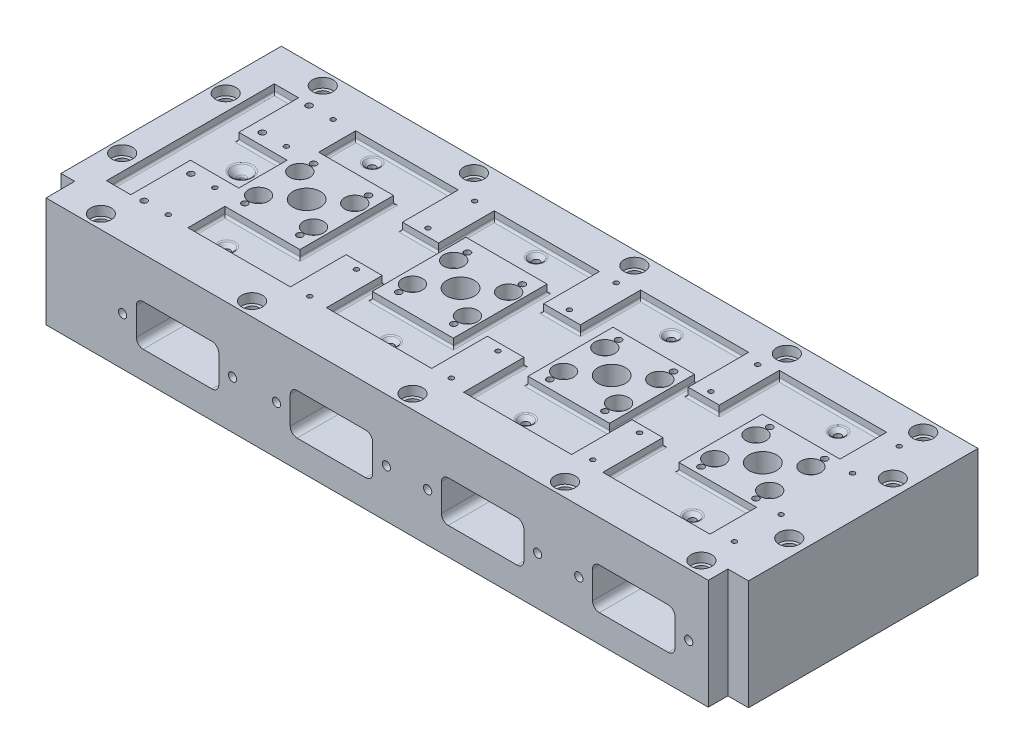
SolidWorks part; units mm, degrees
ref_plane "Alzado" through (0, 0, 0) normal (0, 0, 1) x (1, 0, 0)
ref_plane "Planta" through (0, 0, 0) normal (0, 1, 0) x (1, 0, 0)
ref_plane "Vista lateral" through (0, 0, 0) normal (1, 0, 0) x (0, 0, -1)
sketch "Croquis1" plane through (0, 0, 0) normal (0, 1, 0) x (1, 0, 0)
  line L0 (0, 160.36) -> (0, 0)
  line L1 (0, 0) -> (10, 0)
  line L2 (10, 0) -> (10, -20.92)
  line L3 (10, -20.92) -> (492, -20.92)
  line L4 (492, -20.92) -> (492, -6.67)
  line L5 (492, -6.67) -> (507, -6.67)
  line L6 (507, -6.67) -> (507, 160.36)
  line L7 (507, 160.36) -> (0, 160.36)
  dimension "D1" = 10
  dimension "D2" = 15
  dimension "D3" = 160.36
  dimension "D4" = 507
  dimension "D5" = 14.25
  dimension "D6" = 20.92
extrude "Saliente-Extruir1" add sketch "Croquis1" along normal blind 80
sketch "Croquis2" plane through (0, 80, 0) normal (0, 1, 0) x (1, 0, 0)
  line L0 (507, 160.36) -> (0, 160.36) construction
  line L1 (0, 160.36) -> (0, 0) construction
  line L2 (507, -6.67) -> (507, 160.36) construction
  circle A0 centre (105.75, 75.12) radius 42.9
  circle A1 centre (217.75, 75.12) radius 42.9
  circle A2 centre (327.75, 75.12) radius 42.9
  circle A3 centre (437.75, 75.12) radius 42.9
  point P13 (0, 80.18)
  dimension "D1" = 85.8
  dimension "D2" = 85.24
  dimension "D3" = 105.75
  dimension "D4" = 112
  dimension "D5" = 110
  dimension "D6" = 69.25
sketch "Croquis3" plane through (0, 0, 0) normal (0, -1, 0) x (1, 0, 0)
  circle A0 centre (437.75, -75.12) radius 42.9 construction
  circle A1 centre (327.75, -75.12) radius 42.9 construction
  circle A2 centre (217.75, -75.12) radius 42.9 construction
  circle A3 centre (105.75, -75.12) radius 42.9 construction
  circle A4 centre (437.75, -75.12) radius 42.9
  circle A5 centre (327.75, -75.12) radius 42.9
  circle A6 centre (217.75, -75.12) radius 42.9
  circle A7 centre (105.75, -75.12) radius 42.9
extrude "Cortar-Extruir2" cut sketch "Croquis3" against normal blind 1.5
sketch "Croquis4" plane through (0, 80, 0) normal (0, 1, 0) x (1, 0, 0)
  circle A0 centre (105.75, 75.12) radius 42.9 construction
  circle A1 centre (217.75, 75.12) radius 42.9 construction
  circle A2 centre (327.75, 75.12) radius 42.9 construction
  circle A3 centre (437.75, 75.12) radius 42.9 construction
  circle A4 centre (105.75, 75.12) radius 42.9
  circle A5 centre (217.75, 75.12) radius 42.9
  circle A6 centre (327.75, 75.12) radius 42.9
  circle A7 centre (437.75, 75.12) radius 42.9
sketch "Croquis5" plane through (0, 80, 0) normal (0, 1, 0) x (1, 0, 0)
  line L0 (85.75, 58.02) -> (125.75, 58.02) construction
  line L1 (197.75, 58.02) -> (237.75, 58.02) construction
  line L2 (307.75, 58.02) -> (347.75, 58.02) construction
  line L3 (417.75, 58.02) -> (457.75, 58.02) construction
  circle A0 centre (437.75, 75.12) radius 42.9 construction
  circle A1 centre (327.75, 75.12) radius 42.9 construction
  circle A2 centre (217.75, 75.12) radius 42.9 construction
  circle A3 centre (105.75, 75.12) radius 42.9 construction
  circle A4 centre (437.75, 75.12) radius 42.9 construction
  circle A5 centre (327.75, 75.12) radius 42.9 construction
  circle A6 centre (217.75, 75.12) radius 42.9 construction
  circle A7 centre (105.75, 75.12) radius 42.9 construction
  circle A8 centre (85.75, 88.02) radius 3
  circle A9 centre (125.75, 88.02) radius 3
  circle A10 centre (85.75, 58.02) radius 3
  circle A11 centre (125.75, 58.02) radius 3
  circle A12 centre (237.75, 88.02) radius 3
  circle A13 centre (197.75, 58.02) radius 3
  circle A14 centre (237.75, 58.02) radius 3
  circle A15 centre (197.75, 88.02) radius 3
  circle A16 centre (347.75, 88.02) radius 3
  circle A17 centre (307.75, 58.02) radius 3
  circle A18 centre (347.75, 58.02) radius 3
  circle A19 centre (307.75, 88.02) radius 3
  circle A20 centre (457.75, 88.02) radius 3
  circle A21 centre (417.75, 58.02) radius 3
  circle A22 centre (457.75, 58.02) radius 3
  circle A23 centre (417.75, 88.02) radius 3
  point P20 (105.75, 58.02)
  point P21 (105.75, 118.02)
  point P22 (217.75, 118.02)
  point P23 (327.75, 118.02)
  point P24 (437.75, 118.02)
  point P33 (437.75, 58.02)
  point P42 (327.75, 58.02)
  point P53 (217.75, 58.02)
  point P54 (437.75, 75.12)
  point P55 (217.75, 58.02)
  point P56 (437.75, 58.02)
  point P57 (327.75, 58.02)
  dimension "D3" = 6
  dimension "D8" = 6
  dimension "D10" = 30
  dimension "D12" = 6
  dimension "D14" = 6
  dimension "D15" = 30
  dimension "D1" = 30
  dimension "D2" = 40
  dimension "D4" = 30
  dimension "D5" = 30
  dimension "D6" = 40
  dimension "D7" = 30
  dimension "D9" = 40
  dimension "D11" = 30
  dimension "D13" = 40
  dimension "D16" = 30
extrude "Cortar-Extruir3" cut sketch "Croquis5" against normal blind 77
sketch "Croquis6" plane through (0, 1.5, 0) normal (0, -1, 0) x (1, 0, 0)
  circle A0 centre (85.75, -88.02) radius 14
  circle A1 centre (125.75, -88.02) radius 14
  circle A2 centre (125.75, -58.02) radius 14
  circle A4 centre (85.75, -58.02) radius 14
  circle A5 centre (197.75, -58.02) radius 14
  circle A6 centre (197.75, -88.02) radius 14
  circle A7 centre (237.75, -88.02) radius 14
  circle A8 centre (237.75, -58.02) radius 14
  circle A9 centre (307.75, -58.02) radius 14
  circle A10 centre (307.75, -88.02) radius 14
  circle A11 centre (347.75, -88.02) radius 14
  circle A12 centre (347.75, -58.02) radius 14
  circle A13 centre (457.75, -88.02) radius 14
  circle A14 centre (417.75, -88.02) radius 14
  circle A15 centre (417.75, -58.02) radius 14
  circle A17 centre (457.75, -58.02) radius 14
  dimension "D1" = 28
extrude "Cortar-Extruir4" cut sketch "Croquis6" against normal up to surface (1.5 mm away) up to face at (85.75, 3, -55.02)
chamfer "Chaflán1" distance 1.5 distance2 10 16 edges at (417.75, 3, -44.02) (457.75, 3, -44.02) (457.75, 3, -74.02) (417.75, 3, -74.02) (307.75, 3, -74.02) (307.75, 3, -44.02) (347.75, 3, -74.02) (347.75, 3, -44.02) (237.75, 3, -74.02) (237.75, 3, -44.02) (197.75, 3, -74.02) (197.75, 3, -44.02) (125.75, 3, -44.02) (85.75, 3, -44.02) (125.75, 3, -74.02) (85.75, 3, -74.02)
sketch "Croquis7" plane through (0, 0, 20.92) normal (0, 0, 1) x (1, 0, 0)
  line L0 (10, 0) -> (492, 0) construction
  line L1 (80.75, 50) -> (130.75, 50)
  line L2 (75.75, 45) -> (75.75, 25)
  line L3 (80.75, 20) -> (130.75, 20)
  line L4 (135.75, 45) -> (135.75, 25)
  line L5 (75.75, 50) -> (135.75, 20) construction
  line L6 (75.75, 20) -> (135.75, 50) construction
  line L7 (192.75, 50) -> (242.75, 50)
  line L8 (187.75, 45) -> (187.75, 25)
  line L9 (192.75, 20) -> (242.75, 20)
  line L10 (247.75, 45) -> (247.75, 25)
  line L11 (187.75, 50) -> (247.75, 20) construction
  line L12 (187.75, 20) -> (247.75, 50) construction
  line L13 (302.75, 50) -> (352.75, 50)
  line L14 (297.75, 45) -> (297.75, 25)
  line L15 (302.75, 20) -> (352.75, 20)
  line L16 (357.75, 45) -> (357.75, 25)
  line L17 (297.75, 50) -> (357.75, 20) construction
  line L18 (297.75, 20) -> (357.75, 50) construction
  line L19 (412.75, 50) -> (462.75, 50)
  line L20 (407.75, 45) -> (407.75, 25)
  line L21 (412.75, 20) -> (462.75, 20)
  line L22 (467.75, 45) -> (467.75, 25)
  line L23 (407.75, 50) -> (467.75, 20) construction
  line L24 (407.75, 20) -> (467.75, 50) construction
  arc A0 (130.75, 50) -> (135.75, 45) centre (130.75, 45) cw
  arc A1 (130.75, 20) -> (135.75, 25) centre (130.75, 25) ccw
  arc A2 (80.75, 50) -> (75.75, 45) centre (80.75, 45) ccw
  arc A3 (75.75, 25) -> (80.75, 20) centre (80.75, 25) ccw
  arc A4 (192.75, 50) -> (187.75, 45) centre (192.75, 45) ccw
  arc A5 (242.75, 50) -> (247.75, 45) centre (242.75, 45) cw
  arc A6 (242.75, 20) -> (247.75, 25) centre (242.75, 25) ccw
  arc A7 (187.75, 25) -> (192.75, 20) centre (192.75, 25) ccw
  arc A8 (462.75, 50) -> (467.75, 45) centre (462.75, 45) cw
  arc A9 (462.75, 20) -> (467.75, 25) centre (462.75, 25) ccw
  arc A10 (412.75, 50) -> (407.75, 45) centre (412.75, 45) ccw
  arc A11 (407.75, 25) -> (412.75, 20) centre (412.75, 25) ccw
  arc A12 (297.75, 25) -> (302.75, 20) centre (302.75, 25) ccw
  arc A13 (352.75, 50) -> (357.75, 45) centre (352.75, 45) cw
  arc A14 (352.75, 20) -> (357.75, 25) centre (352.75, 25) ccw
  arc A15 (302.75, 50) -> (297.75, 45) centre (302.75, 45) ccw
  point P0 (105.75, 35)
  point P5 (217.75, 35)
  point P10 (327.75, 35)
  point P15 (437.75, 35)
  point P23 (437.75, 80)
  point P24 (327.75, 80)
  point P27 (217.75, 80)
  point P29 (105.75, 80)
  dimension "D4" = 5
  dimension "D1" = 30
  dimension "D2" = 60
  dimension "D3" = 20
extrude "Cortar-Extruir5" cut sketch "Croquis7" against normal blind 100
sketch "Croquis8" plane through (0, 0, -160.36) normal (0, 0, -1) x (-1, 0, 0)
  line L0 (-462.75, 50) -> (-412.75, 50) construction
  line L1 (-407.75, 45) -> (-407.75, 25) construction
  line L2 (-412.75, 20) -> (-462.75, 20) construction
  line L3 (-467.75, 25) -> (-467.75, 45) construction
  line L4 (-302.75, 20) -> (-352.75, 20) construction
  line L5 (-357.75, 25) -> (-357.75, 45) construction
  line L6 (-352.75, 50) -> (-302.75, 50) construction
  line L7 (-297.75, 45) -> (-297.75, 25) construction
  line L8 (-187.75, 45) -> (-187.75, 25) construction
  line L9 (-192.75, 20) -> (-242.75, 20) construction
  line L10 (-247.75, 25) -> (-247.75, 45) construction
  line L11 (-242.75, 50) -> (-192.75, 50) construction
  line L12 (-130.75, 50) -> (-80.75, 50) construction
  line L13 (-75.75, 45) -> (-75.75, 25) construction
  line L14 (-80.75, 20) -> (-130.75, 20) construction
  line L15 (-135.75, 25) -> (-135.75, 45) construction
  line L16 (-462.75, 50) -> (-412.75, 50)
  line L17 (-407.75, 45) -> (-407.75, 25)
  line L18 (-412.75, 20) -> (-462.75, 20)
  line L19 (-467.75, 25) -> (-467.75, 45)
  line L20 (-302.75, 20) -> (-352.75, 20)
  line L21 (-357.75, 25) -> (-357.75, 45)
  line L22 (-352.75, 50) -> (-302.75, 50)
  line L23 (-297.75, 45) -> (-297.75, 25)
  line L24 (-187.75, 45) -> (-187.75, 25)
  line L25 (-192.75, 20) -> (-242.75, 20)
  line L26 (-247.75, 25) -> (-247.75, 45)
  line L27 (-242.75, 50) -> (-192.75, 50)
  line L28 (-130.75, 50) -> (-80.75, 50)
  line L29 (-75.75, 45) -> (-75.75, 25)
  line L30 (-80.75, 20) -> (-130.75, 20)
  line L31 (-135.75, 25) -> (-135.75, 45)
  arc A0 (-462.75, 50) -> (-467.75, 45) centre (-462.75, 45) ccw construction
  arc A1 (-407.75, 45) -> (-412.75, 50) centre (-412.75, 45) ccw construction
  arc A2 (-412.75, 20) -> (-407.75, 25) centre (-412.75, 25) ccw construction
  arc A3 (-467.75, 25) -> (-462.75, 20) centre (-462.75, 25) ccw construction
  arc A4 (-302.75, 20) -> (-297.75, 25) centre (-302.75, 25) ccw construction
  arc A5 (-357.75, 25) -> (-352.75, 20) centre (-352.75, 25) ccw construction
  arc A6 (-352.75, 50) -> (-357.75, 45) centre (-352.75, 45) ccw construction
  arc A7 (-297.75, 45) -> (-302.75, 50) centre (-302.75, 45) ccw construction
  arc A8 (-187.75, 45) -> (-192.75, 50) centre (-192.75, 45) ccw construction
  arc A9 (-192.75, 20) -> (-187.75, 25) centre (-192.75, 25) ccw construction
  arc A10 (-247.75, 25) -> (-242.75, 20) centre (-242.75, 25) ccw construction
  arc A11 (-242.75, 50) -> (-247.75, 45) centre (-242.75, 45) ccw construction
  arc A12 (-130.75, 50) -> (-135.75, 45) centre (-130.75, 45) ccw construction
  arc A13 (-75.75, 45) -> (-80.75, 50) centre (-80.75, 45) ccw construction
  arc A14 (-80.75, 20) -> (-75.75, 25) centre (-80.75, 25) ccw construction
  arc A15 (-135.75, 25) -> (-130.75, 20) centre (-130.75, 25) ccw construction
  arc A16 (-462.75, 50) -> (-467.75, 45) centre (-462.75, 45) ccw
  arc A17 (-407.75, 45) -> (-412.75, 50) centre (-412.75, 45) ccw
  arc A18 (-412.75, 20) -> (-407.75, 25) centre (-412.75, 25) ccw
  arc A19 (-467.75, 25) -> (-462.75, 20) centre (-462.75, 25) ccw
  arc A20 (-302.75, 20) -> (-297.75, 25) centre (-302.75, 25) ccw
  arc A21 (-357.75, 25) -> (-352.75, 20) centre (-352.75, 25) ccw
  arc A22 (-352.75, 50) -> (-357.75, 45) centre (-352.75, 45) ccw
  arc A23 (-297.75, 45) -> (-302.75, 50) centre (-302.75, 45) ccw
  arc A24 (-187.75, 45) -> (-192.75, 50) centre (-192.75, 45) ccw
  arc A25 (-192.75, 20) -> (-187.75, 25) centre (-192.75, 25) ccw
  arc A26 (-247.75, 25) -> (-242.75, 20) centre (-242.75, 25) ccw
  arc A27 (-242.75, 50) -> (-247.75, 45) centre (-242.75, 45) ccw
  arc A28 (-130.75, 50) -> (-135.75, 45) centre (-130.75, 45) ccw
  arc A29 (-75.75, 45) -> (-80.75, 50) centre (-80.75, 45) ccw
  arc A30 (-80.75, 20) -> (-75.75, 25) centre (-80.75, 25) ccw
  arc A31 (-135.75, 25) -> (-130.75, 20) centre (-130.75, 25) ccw
extrude "Cortar-Extruir6" cut sketch "Croquis8" against normal blind 78.59
sketch "Croquis9" plane through (0, 1.5, 0) normal (0, -1, 0) x (1, 0, 0)
  circle A0 centre (85.75, -58.02) radius 7.5
  circle A1 centre (125.75, -58.02) radius 7.5
  circle A2 centre (85.75, -88.02) radius 7.5
  circle A3 centre (125.75, -88.02) radius 7.5
  circle A4 centre (197.75, -88.02) radius 7.5
  circle A5 centre (197.75, -58.02) radius 7.5
  circle A6 centre (237.75, -88.02) radius 7.5
  circle A7 centre (237.75, -58.02) radius 7.5
  circle A8 centre (347.75, -58.02) radius 7.5
  circle A9 centre (307.75, -58.02) radius 7.5
  circle A10 centre (307.75, -88.02) radius 7.5
  circle A11 centre (347.75, -88.02) radius 7.5
  circle A12 centre (417.75, -58.02) radius 7.5
  circle A13 centre (417.75, -88.02) radius 7.5
  circle A14 centre (457.75, -88.02) radius 7.5
  circle A15 centre (457.75, -58.02) radius 7.5
  dimension "D1" = 15
extrude "Cortar-Extruir7" cut sketch "Croquis9" against normal up to surface (48.5 mm away) up to face at (85.75, 50, -55.02)
sketch "Croquis10" plane through (0, 80, 0) normal (0, 1, 0) x (1, 0, 0)
  line L0 (0, 140.61) -> (19, 140.61) construction
  line L1 (0, 160.36) -> (0, 0) construction
  line L2 (19, 140.61) -> (19, 160.36) construction
  line L3 (507, 160.36) -> (0, 160.36) construction
  line L4 (0, 0) -> (10, 0) construction
  line L5 (507, -6.67) -> (507, 160.36) construction
  line L6 (507, 160.36) -> (483, 160.36) construction
  line L7 (10, -20.92) -> (10, -1.01) construction
  point P0 (40, -10.965)
  point P1 (150, -10.965)
  point P2 (266.75, -10.965)
  point P3 (377.75, -10.965)
  point P4 (477, -10.965)
  point P5 (495, 35)
  point P6 (495, 110.36)
  point P7 (477, 150.485)
  point P8 (377.75, 150.485)
  point P9 (266.75, 150.485)
  point P10 (150, 150.485)
  point P11 (40, 150.485)
  point P12 (9.5, 110.36)
  point P13 (9.5, 35)
  point P19 (495, 160.36)
  point P24 (9.5, 140.61)
  point P33 (10, -10.965)
  point P34 (19, 150.485)
  dimension "D1" = 19.75
  dimension "D2" = 19
  dimension "D3" = 35
  dimension "D4" = 50
  dimension "D5" = 40
  dimension "D6" = 110
  dimension "D7" = 116.75
  dimension "D8" = 111
  dimension "D9" = 30
  dimension "D10" = 24
  dimension "D11" = 19.91
hole_wizard "Refrentado para perno con cabeza hexagonal de M101" positions "Croquis3D1" profile "Croquis11" counterbore size "M10" standard "Ansi Metric"
sketch3d "Croquis3D1"
  point P0 (40, 80, -150.485)
  point P3 (9.5, 80, -110.36)
  point P6 (9.5, 80, -35)
  point P9 (40, 80, 10.965)
  point P12 (150, 80, 10.965)
  point P15 (266.75, 80, 10.965)
  point P18 (377.75, 80, 10.965)
  point P21 (477, 80, 10.965)
  point P24 (495, 80, -35)
  point P27 (495, 80, -110.36)
  point P30 (477, 80, -150.485)
  point P33 (377.75, 80, -150.485)
  point P36 (266.75, 80, -150.485)
  point P39 (150, 80, -150.485)
sketch "Croquis11" plane through (40, 80, -150.485) normal (1, 0, 0) x (0, 0, 1)
  line L0 (0, 0) -> (0, 93.1545)
  line L1 (0, 93.1545) -> (5.25, 90)
  line L2 (5.25, 90) -> (5.25, 6.85)
  line L3 (5.25, 6.85) -> (7.5, 6.85)
  line L4 (7.5, 6.85) -> (7.5, 0)
  line L5 (7.5, 0) -> (0, 0)
  line L10 (0, 93.1545) -> (-5.25, 90) construction
  line L11 (0, -6.35) -> (0, 107.95) construction
  dimension "Diámetro de taladro" = 10.5
  dimension "Profundidad de taladro" = 90
  dimension "Diámetro de refrentado" = 15
  dimension "Profundidad de refrentado" = 6.85
  dimension "Ángulo de perforador" = 118
sketch "Croquis12" plane through (0, 80, 0) normal (0, 1, 0) x (1, 0, 0)
  line L0 (477, 99.02) -> (477, 133.02) construction
  line L2 (507, -6.67) -> (507, 160.36) construction
  line L3 (374, 99.02) -> (374, 133.02) construction
  line L4 (271, 99.02) -> (271, 133.02) construction
  line L5 (168, 99.02) -> (168, 133.02) construction
  line L6 (65, 99.02) -> (65, 133.02) construction
  line L7 (417.75, 58.02) -> (417.75, 88.02) construction
  line L8 (417.75, 73.02) -> (362.9429, 73.02) construction
  circle A0 centre (457.75, 88.02) radius 3 construction
  circle A1 centre (417.75, 88.02) radius 3 construction
  point P2 (477, 116.02)
  point P17 (374, 116.02)
  dimension "D1" = 28
  dimension "D2" = 34
  dimension "D3" = 30
  dimension "D5" = 103
  dimension "D6" = 28
  dimension "D4" = 5
hole_wizard "Taladro de margen para M31" positions "Croquis3D2" profile "Croquis13" hole size "M3" standard "Ansi Metric"
sketch3d "Croquis3D2"
  point P0 (65, 80, -133.02)
  point P3 (65, 80, -99.02)
  point P6 (168, 80, -133.02)
  point P9 (168, 80, -99.02)
  point P12 (271, 80, -133.02)
  point P15 (271, 80, -99.02)
  point P18 (374, 80, -133.02)
  point P21 (374, 80, -99.02)
  point P24 (477, 80, -133.02)
  point P27 (477, 80, -99.02)
sketch "Croquis13" plane through (65, 80, -133.02) normal (1, 0, 0) x (0, 0, 1)
  line L0 (0, 0) -> (0, 21.0215)
  line L1 (0, 21.0215) -> (1.7, 20)
  line L2 (1.7, 20) -> (1.7, 0)
  line L5 (1.7, 0) -> (0, 0)
  line L10 (0, 21.0215) -> (-1.7, 20) construction
  line L11 (0, -6.35) -> (0, 107.95) construction
  dimension "Diámetro de taladro" = 3.4
  dimension "Profundidad de taladro" = 20
  dimension "Ángulo de perforador" = 118
ref_plane "Plano1" through (0, 0, -73.02) normal (0, 0, -1) x (-1, 0, 0)
mirror "Simetría1" about plane through (0, 0, -73.02) normal (0, 0, -1) of "Taladro de margen para M31"
sketch "Croquis14" plane through (0, 80, 0) normal (0, 1, 0) x (1, 0, 0)
  line L0 (457.75, 88.02) -> (457.75, 98.02) construction
  line L1 (417.75, 88.02) -> (417.75, 98.02) construction
  line L2 (347.75, 88.02) -> (347.75, 98.02) construction
  line L3 (307.75, 88.02) -> (307.75, 98.02) construction
  line L4 (237.75, 88.02) -> (237.75, 98.02) construction
  line L5 (197.75, 88.02) -> (197.75, 98.02) construction
  line L6 (125.75, 88.02) -> (125.75, 98.02) construction
  line L7 (85.75, 88.02) -> (85.75, 98.02) construction
  dimension "D1" = 10
hole_wizard "Ranura de margen para M41" positions "Croquis15" profile "Croquis16" size "M4" standard "Ansi Metric" slot yes
sketch "Croquis15" plane through (0, 80, 0) normal (0, 1, 0) x (1, 0, 0)
  point P0 (457.75, 98.02)
  point P3 (417.75, 98.02)
  point P6 (347.75, 98.02)
  point P9 (307.75, 98.02)
  point P12 (237.75, 98.02)
  point P15 (197.75, 98.02)
  point P18 (125.75, 98.02)
  point P21 (85.75, 98.02)
sketch "Croquis16" plane through (457.75, 80, -98.02) normal (1, 0, 0) x (0, 0, 1)
  line L0 (0, 0) -> (0, 15)
  line L2 (2.25, 15) -> (2.25, 0)
  line L3 (2.25, 15) -> (0, 15)
  line L5 (2.25, 0) -> (0, 0)
  line L11 (0, -6.35) -> (0, 107.95) construction
  dimension "Diámetro de taladro" = 4.5
  dimension "Profundidad de taladro" = 15
mirror "Simetría2" about plane through (0, 0, -73.02) normal (0, 0, -1) of "Ranura de margen para M41"
sketch "Croquis17" plane through (0, 80, 0) normal (0, 1, 0) x (1, 0, 0)
  circle A1 centre (477, 99.02) radius 1.7 construction
  circle A3 centre (457.75, 98.02) radius 2.25 construction
  circle A4 centre (417.75, 98.02) radius 2.25 construction
  point P1 (456.8267, 100.0718)
  point P2 (418.6733, 100.0718)
  point P8 (478.6723, 98.7142)
sketch "Croquis19" plane through (0, 80, 0) normal (0, 1, 0) x (1, 0, 0)
  line L1 (63.5724, 145.0087) -> (131.2951, 145.0087)
  line L2 (53.5724, 135.0087) -> (53.5724, 13.0811)
  line L3 (63.5724, 3.0811) -> (474.9679, 3.0811)
  line L4 (484.9679, 143.0087) -> (484.9679, 13.0811)
  line L5 (474.8015, 145.0087) -> (482.9679, 145.0087)
  line L6 (371.08, 145.0087) -> (457.3569, 145.0087)
  line L7 (264.0394, 145.0087) -> (353.6354, 145.0087)
  line L8 (148.7396, 145.0087) -> (246.5948, 145.0087)
  line L9 (482.9679, 145.0087) -> (484.9679, 143.0087)
  circle A0 centre (457.75, 48.02) radius 2.25 construction
  arc A1 (457.3569, 145.0087) -> (474.8015, 145.0087) centre (466.0792, 154.5848) ccw
  circle A2 centre (457.75, 58.02) radius 3 construction
  arc A3 (353.6354, 145.0087) -> (371.08, 145.0087) centre (362.3577, 154.5848) ccw
  arc A4 (246.5948, 145.0087) -> (264.0394, 145.0087) centre (255.3171, 154.5848) ccw
  arc A5 (131.2951, 145.0087) -> (148.7396, 145.0087) centre (140.0174, 154.5848) ccw
  arc A6 (63.5724, 145.0087) -> (53.5724, 135.0087) centre (63.5724, 135.0087) ccw
  arc A7 (474.9679, 3.0811) -> (484.9679, 13.0811) centre (474.9679, 13.0811) ccw
  arc A8 (53.5724, 13.0811) -> (63.5724, 3.0811) centre (63.5724, 13.0811) ccw
  point P2 (457.75, 55.02)
  point P4 (457.75, 50.27)
  point P9 (484.9679, 145.0087)
  dimension "D1" = 10
  dimension "D2" = 10
sketch "Croquis20" plane through (0, 80, 0) normal (0, 1, 0) x (1, 0, 0)
  circle A0 centre (85.75, 98.02) radius 4.25
  circle A1 centre (85.75, 98.02) radius 2.75
  circle A2 centre (125.75, 98.02) radius 2.75
  circle A3 centre (125.75, 98.02) radius 4.25
  circle A4 centre (197.75, 98.02) radius 4.25
  circle A5 centre (197.75, 98.02) radius 2.75
  circle A6 centre (237.75, 98.02) radius 2.75
  circle A7 centre (237.75, 98.02) radius 4.25
  circle A8 centre (347.75, 98.02) radius 4.25
  circle A9 centre (347.75, 98.02) radius 2.75
  circle A10 centre (307.75, 98.02) radius 4.25
  circle A11 centre (307.75, 98.02) radius 2.75
  dimension "D1" = 5.5
  dimension "D2" = 8.5
  dimension "D3" = 2
  dimension "D4" = 2
  dimension "D5" = 2
sketch "Croquis21" plane through (0, 80, 0) normal (0, 1, 0) x (1, 0, 0)
  line L0 (457.75, 61.02) -> (457.75, 85.02) construction
  line L1 (457.75, 73.02) -> (376.5015, 73.02) construction
  circle A0 centre (457.75, 58.02) radius 3 construction
  circle A1 centre (457.75, 88.02) radius 3 construction
sketch "Croquis22" plane through (0, 80, 0) normal (0, 1, 0) x (1, 0, 0)
  circle A0 centre (457.75, 58.02) radius 7.3
  circle A1 centre (417.75, 58.02) radius 7.3
  circle A2 centre (347.75, 58.02) radius 7.3
  circle A3 centre (307.75, 58.02) radius 7.3
  circle A4 centre (237.75, 58.02) radius 7.3
  circle A5 centre (197.75, 58.02) radius 7.3
  circle A6 centre (125.75, 58.02) radius 7.3
  circle A7 centre (85.75, 58.02) radius 7.3
  dimension "D1" = 14.6
extrude "Cortar-Extruir8" cut sketch "Croquis22" against normal blind 10
mirror "Simetría3" about plane through (0, 0, -73.02) normal (0, 0, -1) of "Cortar-Extruir8"
sketch "Croquis23" plane through (0, 80, 0) normal (0, 1, 0) x (1, 0, 0)
  line L0 (47.5, 133.02) -> (47.5, 99.02) construction
  line L1 (65, 133.02) -> (56, 133.02) construction
  line L2 (42, 133.02) -> (53, 133.02) construction
  line L3 (65, 133.02) -> (65, 99.02) construction
  point P8 (47.5, 133.02)
  dimension "D1" = 9
  dimension "D2" = 3
  dimension "D3" = 11
hole_wizard "Taladro de margen para M41" positions "Croquis3D4" profile "Croquis25" hole size "M4" standard "Ansi Metric"
sketch3d "Croquis3D4"
  point P0 (47.5, 80, -133.02)
  point P3 (47.5, 80, -99.02)
sketch "Croquis25" plane through (47.5, 80, -133.02) normal (1, 0, 0) x (0, 0, 1)
  line L0 (0, 0) -> (0, 21.3519)
  line L1 (0, 21.3519) -> (2.25, 20)
  line L2 (2.25, 20) -> (2.25, 0)
  line L5 (2.25, 0) -> (0, 0)
  line L10 (0, 21.3519) -> (-2.25, 20) construction
  line L11 (0, -6.35) -> (0, 107.95) construction
  dimension "Diámetro de taladro" = 4.5
  dimension "Profundidad de taladro" = 20
  dimension "Ángulo de perforador" = 118
mirror "Simetría4" about plane through (0, 0, -73.02) normal (0, 0, -1) of "Taladro de margen para M41"
sketch "Croquis26" plane through (0, 80, 0) normal (0, 1, 0) x (1, 0, 0)
  line L1 (85.75, 58.02) -> (125.75, 58.02) construction
  line L2 (85.75, 58.02) -> (85.75, 88.02) construction
  line L3 (85.75, 88.02) -> (125.75, 88.02) construction
  line L4 (125.75, 58.02) -> (125.75, 88.02) construction
  line L5 (85.75, 58.02) -> (125.75, 88.02) construction
  line L6 (85.75, 88.02) -> (125.75, 58.02) construction
  line L7 (197.75, 58.02) -> (237.75, 58.02) construction
  line L8 (197.75, 58.02) -> (197.75, 88.02) construction
  line L9 (197.75, 88.02) -> (237.75, 88.02) construction
  line L10 (237.75, 58.02) -> (237.75, 88.02) construction
  line L11 (197.75, 58.02) -> (237.75, 88.02) construction
  line L12 (197.75, 88.02) -> (237.75, 58.02) construction
  line L13 (307.75, 58.02) -> (347.75, 58.02) construction
  line L14 (307.75, 58.02) -> (307.75, 88.02) construction
  line L15 (307.75, 88.02) -> (347.75, 88.02) construction
  line L16 (347.75, 58.02) -> (347.75, 88.02) construction
  line L17 (307.75, 58.02) -> (347.75, 88.02) construction
  line L18 (307.75, 88.02) -> (347.75, 58.02) construction
  line L19 (417.75, 58.02) -> (457.75, 58.02) construction
  line L20 (417.75, 58.02) -> (417.75, 88.02) construction
  line L21 (417.75, 88.02) -> (457.75, 88.02) construction
  line L22 (457.75, 58.02) -> (457.75, 88.02) construction
  line L23 (417.75, 58.02) -> (457.75, 88.02) construction
  line L24 (417.75, 88.02) -> (457.75, 58.02) construction
  circle A0 centre (85.75, 88.02) radius 7.3 construction
  circle A1 centre (85.75, 58.02) radius 7.3 construction
  circle A2 centre (197.75, 58.02) radius 7.3 construction
  circle A3 centre (307.75, 58.02) radius 7.3 construction
  circle A4 centre (417.75, 58.02) radius 7.3 construction
  circle A5 centre (437.75, 73.02) radius 10
  circle A6 centre (327.75, 73.02) radius 10
  circle A7 centre (217.75, 73.02) radius 10
  circle A8 centre (105.75, 73.02) radius 10
  point P0 (105.75, 73.02)
  point P12 (217.75, 73.02)
  point P19 (327.75, 73.02)
  point P27 (437.75, 73.02)
  dimension "D1" = 20
extrude "Cortar-Extruir9" cut sketch "Croquis26" against normal blind 16
sketch "Croquis27" plane through (0, 64, 0) normal (0, 1, 0) x (1, 0, 0)
  circle A0 centre (105.75, 73.02) radius 4
  circle A1 centre (217.75, 73.02) radius 4
  circle A2 centre (327.75, 73.02) radius 4
  circle A3 centre (437.75, 73.02) radius 4
  dimension "D1" = 8
extrude "Cortar-Extruir10" cut sketch "Croquis27" against normal blind 176
sketch "Croquis28" plane through (0, 20, 0) normal (0, 1, 0) x (1, 0, 0)
  line L1 (62.2092, 80.72) -> (484.9236, 80.72)
  line L2 (62.2092, 80.72) -> (62.2092, 65.32)
  line L3 (62.2092, 65.32) -> (484.9236, 65.32)
  line L4 (484.9236, 80.72) -> (484.9236, 65.32)
  circle A0 centre (457.75, 88.02) radius 7.3 construction
  circle A1 centre (457.75, 58.02) radius 7.3 construction
extrude "Saliente-Extruir2" add sketch "Croquis28" along normal up to surface (30 mm away) up to face at (105.75, 50, -69.02)
sketch "Croquis29" plane through (0, 50, 0) normal (0, 1, 0) x (1, 0, 0)
  circle A1 centre (437.75, 73.02) radius 4
  circle A2 centre (437.75, 73.02) radius 4
  circle A3 centre (327.75, 73.02) radius 4
  circle A4 centre (327.75, 73.02) radius 4
  circle A5 centre (217.75, 73.02) radius 4
  circle A6 centre (217.75, 73.02) radius 4
  circle A7 centre (105.75, 73.02) radius 4
  circle A8 centre (105.75, 73.02) radius 4
  dimension "D1" = 0
  dimension "D2" = 0
  dimension "D3" = 0
  dimension "D4" = 0
extrude "Cortar-Extruir11" cut sketch "Croquis29" against normal blind 176
chamfer "Chaflán2" distance 5 angle 80 4 edges at (105.75, 64, -69.02) (217.75, 64, -69.02) (437.75, 64, -69.02) (327.75, 64, -69.02)
sketch "Croquis30" plane through (0, 80, 0) normal (0, 1, 0) x (1, 0, 0)
  line L0 (463.5288, 103.3724) -> (406.9565, 103.3724)
  line L1 (187.593, 107.1143) -> (246.5986, 107.1143)
  line L2 (187.593, 107.1143) -> (187.593, 73.02)
  line L3 (357.0927, 73.02) -> (406.9565, 73.02)
  line L4 (246.5986, 107.1143) -> (246.5986, 73.02)
  line L5 (297.7922, 103.9445) -> (357.0927, 103.9445)
  line L6 (297.7922, 103.9445) -> (297.7922, 73.02)
  line L7 (21.1598, 134.0966) -> (38.8141, 134.0966)
  line L8 (357.0927, 103.9445) -> (357.0927, 73.02)
  line L9 (385.5468, 137.2704) -> (463.5288, 137.2704)
  line L10 (385.5468, 137.2704) -> (385.5468, 93.5024)
  line L11 (406.9565, 103.3724) -> (406.9565, 73.02)
  line L12 (463.5288, 137.2704) -> (463.5288, 103.3724)
  line L13 (385.5468, 93.5024) -> (362.9687, 93.5024)
  line L14 (362.9687, 93.5024) -> (362.9687, 137.4302)
  line L15 (362.9687, 137.4302) -> (284.4159, 137.4302)
  line L16 (284.4159, 137.4302) -> (284.4159, 93.5024)
  line L17 (284.4159, 93.5024) -> (257.7842, 93.5024)
  line L18 (257.7842, 93.5024) -> (257.7842, 134.0966)
  line L19 (257.7842, 134.0966) -> (181.2297, 134.0966)
  line L20 (181.2297, 134.0966) -> (181.2297, 93.5024)
  line L21 (181.2297, 93.5024) -> (154.979, 93.5024)
  line L22 (154.979, 93.5024) -> (154.979, 134.0966)
  line L23 (154.979, 134.0966) -> (80.4071, 134.0966)
  line L24 (80.4071, 134.0966) -> (80.4071, 107.1143)
  line L25 (80.4071, 107.1143) -> (134.936, 107.1143)
  line L26 (134.936, 107.1143) -> (134.936, 73.02)
  line L27 (134.936, 73.02) -> (217.75, 73.02) construction
  line L28 (134.936, 73.02) -> (187.593, 73.02)
  line L29 (246.5986, 73.02) -> (297.7922, 73.02)
  line L30 (38.8141, 134.0966) -> (38.8141, 90.6145)
  line L31 (38.8141, 90.6145) -> (73.9375, 90.6145)
  line L32 (73.9375, 90.6145) -> (73.9375, 73.02)
  line L33 (73.9375, 73.02) -> (21.1598, 73.02)
  line L34 (21.1598, 73.02) -> (21.1598, 134.0966)
extrude "Cortar-Extruir12" cut sketch "Croquis30" against normal blind 6
mirror "Simetría5" about plane through (0, 0, -73.02) normal (0, 0, -1) of "Cortar-Extruir12"
sketch "Croquis31" plane through (0, 0, 0) normal (-1, 0, 0) x (0, 0, 1)
  line L0 (-27.5, 80) -> (-42.5, 80) construction
  line L1 (-102.86, 80) -> (-117.86, 80) construction
  line L2 (-27.5, 80) -> (-42.5, 80)
  line L3 (-102.86, 80) -> (-117.86, 80)
  line L5 (-125.9783, 80) -> (-125.9783, 64.9998) construction
  line L6 (-117.86, 80) -> (-134.0966, 80) construction
  circle A0 centre (-125.9783, 64.9998) radius 2.5
  dimension "D1" = 15.0002
  dimension "D2" = 5
extrude "Cortar-Extruir13" cut sketch "Croquis31" against normal blind 443 contours A0
sketch "Croquis32" plane through (0, 80, 0) normal (0, 1, 0) x (1, 0, 0)
  line L0 (0, 125.9783) -> (439.5, 125.9783) construction
  line L1 (0, 117.86) -> (0, 134.0966) construction
  circle A0 centre (100.5712, 125.9783) radius 2.5
  circle A1 centre (219.75, 125.9783) radius 2.5
  circle A2 centre (318.1703, 125.9783) radius 2.5
  circle A3 centre (439.5, 125.9783) radius 2.5
  dimension "D2" = 5
  dimension "D1" = 439.5
extrude "Cortar-Extruir14" cut sketch "Croquis32" against normal blind 15
chamfer "Chaflán3" distance 3 angle 45 4 edges at (100.5712, 74, -123.4783) (219.75, 74, -123.4783) (318.1703, 74, -123.4783) (439.5, 74, -123.4783)
mirror "Simetría8" about plane through (0, 0, -73.02) normal (0, 0, -1) of "Cortar-Extruir14", "Chaflán3"
mirror "Simetría9" about plane through (0, 0, -73.02) normal (0, 0, -1) of "Cortar-Extruir13"
sketch "Croquis33" plane through (0, 0, 0) normal (-1, 0, 0) x (0, 0, 1)
  line L0 (-125.9783, 64.9998) -> (-20.0617, 64.9998) construction
  circle A0 centre (-73.02, 64.9998) radius 2.5
  dimension "D1" = 5
extrude "Cortar-Extruir15" cut sketch "Croquis33" against normal blind 61
sketch "Croquis34" plane through (0, 80, 0) normal (0, 1, 0) x (1, 0, 0)
  line L0 (0, 75.52) -> (0, 70.52) construction
  line L1 (0, 75.52) -> (0, 70.52)
  line L2 (0, 73.02) -> (58.5, 73.02) construction
  circle A0 centre (58.5, 73.02) radius 2.5
  dimension "D1" = 5
  dimension "D2" = 58.5
extrude "Cortar-Extruir16" cut sketch "Croquis34" against normal blind 15
chamfer "Chaflán4" distance 5 angle 45 1 edges at (58.5, 74, -75.52)
fillet "Redondeo1" radius 2 1 edges at (58.5, 69, -75.52)
fillet "Redondeo3" radius 1.5 61 edges at (29.9869, 74, -134.0966) (38.8141, 74, -112.3555) (56.3758, 74, -90.6145) (73.9375, 74, -73.02) (56.3758, 74, -55.4255) (38.8141, 74, -33.6845) (29.9869, 74, -11.9434) (21.1598, 74, -73.02) (58.5, 74, -80.52) (217.0958, 74, -38.9257) (246.5986, 74, -73.02) (217.0958, 74, -107.1143) (187.593, 74, -73.02) (463.5288, 74, -25.7186) (424.5378, 74, -8.7696) (385.5468, 74, -30.6536) (374.2578, 74, -52.5376) (362.9687, 74, -30.5737) (323.6923, 74, -8.6098) (284.4159, 74, -30.5737) (271.1001, 74, -52.5376) (257.7842, 74, -32.2405) (219.5069, 74, -11.9434) (181.2297, 74, -32.2405) (168.1043, 74, -52.5376) (154.979, 74, -32.2405) (117.693, 74, -11.9434) (80.4071, 74, -25.4345) (107.6715, 74, -38.9257) (134.936, 74, -73.02) (107.6715, 74, -107.1143) (80.4071, 74, -120.6055) (117.693, 74, -134.0966) (154.979, 74, -113.7995) (168.1043, 74, -93.5024) (181.2297, 74, -113.7995) (219.5069, 74, -134.0966) (257.7842, 74, -113.7995) (271.1001, 74, -93.5024) (284.4159, 74, -115.4663) (323.6923, 74, -137.4302) (362.9687, 74, -115.4663) (374.2578, 74, -93.5024) (385.5468, 74, -115.3864) (424.5378, 74, -137.2704) (463.5288, 74, -120.3214) (435.2427, 74, -103.3724) (406.9565, 74, -73.02) (435.2427, 74, -42.6676) (357.0927, 74, -73.02) (327.4425, 74, -103.9445) (297.7922, 74, -73.02) (327.4425, 74, -42.0955) (439.5, 74, -120.4783) (318.1703, 74, -120.4783) (219.75, 74, -120.4783) (100.5712, 74, -120.4783) (439.5, 74, -14.5617) (318.1703, 74, -14.5617) (219.75, 74, -14.5617) (100.5712, 74, -14.5617)
sketch "Croquis35" plane through (0, 0, 0) normal (-1, 0, 0) x (0, 0, 1)
  line L0 (18.465, 80) -> (3.465, 80) construction
  line L1 (-134.0966, 80) -> (-11.9434, 80) construction
  line L2 (-142.985, 80) -> (-157.985, 80) construction
  line L3 (18.465, 80) -> (3.465, 80)
  line L4 (-134.0966, 80) -> (-11.9434, 80)
  line L5 (-142.985, 80) -> (-157.985, 80)
  line L6 (-142.985, 80) -> (-134.0966, 80)
  line L8 (-11.9434, 80) -> (3.465, 80)
sketch "Croquis36" plane through (0, 0, -160.36) normal (0, 0, -1) x (-1, 0, 0)
  line L0 (-2, 80) -> (-17, 80) construction
  line L2 (-2, 80) -> (-17, 80)
  line L3 (-38.8141, 80) -> (-21.1598, 80) construction
  line L4 (-38.8141, 80) -> (-21.1598, 80)
  line L6 (-21.1598, 80) -> (-17, 80) construction
  line L7 (0, 80) -> (0, 0) construction
  line L8 (-507, 80) -> (0, 80) construction
  line L9 (-507, 80) -> (-507, 0) construction
  line L10 (-487.5, 80) -> (-502.5, 80) construction
  line L11 (-487.5, 80) -> (-502.5, 80)
  line L12 (-487.5, 80) -> (-486, 80) construction
  point P4 (-19.0799, 80)
  point P7 (-486, 80)
  dimension "D1" = 19.0799
  dimension "D2" = 21
sketch "Croquis37" plane through (507, 0, 0) normal (1, 0, 0) x (0, 0, -1)
  line L0 (134.72, 80) -> (131.32, 80) construction
  line L1 (100.72, 80) -> (97.32, 80) construction
  line L2 (48.72, 80) -> (45.32, 80) construction
  line L3 (14.72, 80) -> (11.32, 80) construction
  line L4 (134.72, 80) -> (131.32, 80)
  line L5 (100.72, 80) -> (97.32, 80)
  line L6 (48.72, 80) -> (45.32, 80)
  line L7 (14.72, 80) -> (11.32, 80)
  line L8 (45.32, 80) -> (14.72, 80) construction
  line L9 (100.72, 80) -> (131.32, 80) construction
  line L10 (-6.67, 80) -> (-6.67, 0) construction
  line L11 (160.36, 80) -> (160.36, 0) construction
  point P8 (30.02, 80)
  point P11 (116.02, 80)
  dimension "D1" = 36.69
  dimension "D2" = 44.34
sketch "Sketch1" plane through (0, 0, -160.36) normal (0, 0, -1) x (-1, 0, 0)
  line L0 (-498.2742, 32) -> (-24.3165, 32) construction
  line L1 (-507, 0) -> (0, 0) construction
  line L2 (-467.75, 45) -> (-467.75, 25) construction
  line L3 (-407.75, 25) -> (-407.75, 45) construction
  line L4 (-357.75, 45) -> (-357.75, 25) construction
  line L5 (-297.75, 25) -> (-297.75, 45) construction
  line L6 (-247.75, 45) -> (-247.75, 25) construction
  line L7 (-187.75, 25) -> (-187.75, 45) construction
  line L8 (-135.75, 45) -> (-135.75, 25) construction
  line L9 (-75.75, 25) -> (-75.75, 45) construction
  circle A0 centre (-477.75, 32) radius 3
  circle A1 centre (-397.75, 32) radius 3
  circle A2 centre (-367.75, 32) radius 3
  circle A3 centre (-287.75, 32) radius 3
  circle A4 centre (-257.75, 32) radius 3
  circle A5 centre (-177.75, 32) radius 3
  circle A6 centre (-145.75, 32) radius 3
  circle A7 centre (-65.75, 32) radius 3
  dimension "D2" = 6
  dimension "D3" = 10
  dimension "D4" = 6
  dimension "D5" = 10
  dimension "D6" = 6
  dimension "D7" = 10
  dimension "D8" = 6
  dimension "D9" = 10
  dimension "D10" = 6
  dimension "D11" = 10
  dimension "D12" = 6
  dimension "D13" = 10
  dimension "D14" = 6
  dimension "D15" = 10
  dimension "D16" = 6
  dimension "D17" = 10
  dimension "D1" = 32
extrude "Cut-Extrude1" cut sketch "Sketch1" against normal blind 5
sketch "Sketch2" plane through (0, 0, 20.92) normal (0, 0, 1) x (1, 0, 0)
  line L0 (23.5115, 35) -> (480.1846, 35) construction
  line L1 (80.75, 50) -> (130.75, 50) construction
  line L2 (75.75, 45) -> (75.75, 25) construction
  line L3 (135.75, 25) -> (135.75, 45) construction
  line L4 (187.75, 45) -> (187.75, 25) construction
  line L5 (247.75, 25) -> (247.75, 45) construction
  line L6 (297.75, 45) -> (297.75, 25) construction
  line L7 (357.75, 25) -> (357.75, 45) construction
  line L8 (407.75, 45) -> (407.75, 25) construction
  line L9 (467.75, 25) -> (467.75, 45) construction
  circle A0 centre (65.75, 35) radius 3
  circle A1 centre (145.75, 35) radius 3
  circle A2 centre (177.75, 35) radius 3
  circle A3 centre (257.75, 35) radius 3
  circle A4 centre (287.75, 35) radius 3
  circle A5 centre (367.75, 35) radius 3
  circle A6 centre (397.75, 35) radius 3
  circle A7 centre (477.75, 35) radius 3
  dimension "D2" = 6
  dimension "D3" = 10
  dimension "D4" = 6
  dimension "D5" = 10
  dimension "D6" = 6
  dimension "D7" = 10
  dimension "D8" = 6
  dimension "D9" = 10
  dimension "D10" = 6
  dimension "D11" = 10
  dimension "D12" = 6
  dimension "D13" = 10
  dimension "D14" = 6
  dimension "D15" = 10
  dimension "D16" = 6
  dimension "D17" = 10
  dimension "D1" = 15
extrude "Cut-Extrude2" cut sketch "Sketch2" against normal blind 5
